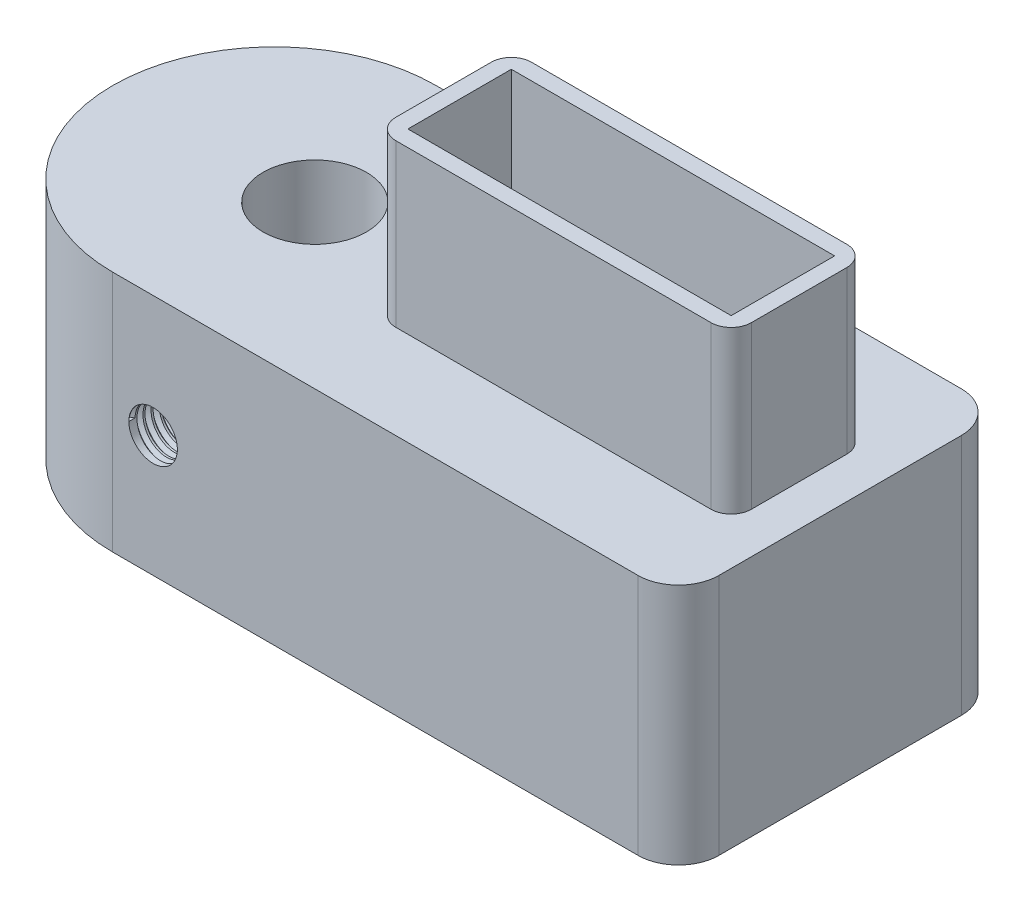
SolidWorks part; units mm, degrees
ref_plane "Front Plane" through (0, 0, 0) normal (0, 0, 1) x (1, 0, 0)
ref_plane "Top Plane" through (0, 0, 0) normal (0, 1, 0) x (1, 0, 0)
ref_plane "Right Plane" through (0, 0, 0) normal (1, 0, 0) x (0, 0, -1)
sketch "Sketch1" plane through (0, 0, 0) normal (0, 1, 0) x (1, 0, 0)
  line L1 (-22.5, 10) -> (22.5, 10)
  line L2 (-22.5, 10) -> (-22.5, -10)
  line L3 (-22.5, -10) -> (22.5, -10)
  line L4 (22.5, 10) -> (22.5, -10)
  line L5 (-22.5, 10) -> (22.5, -10) construction
  line L6 (-22.5, -10) -> (22.5, 10) construction
  point P0 (0, 0)
  dimension "D1" = 45
  dimension "D2" = 20
extrude "Boss-Extrude1" add sketch "Sketch1" along normal blind 15
sketch "Sketch2" plane through (0, 15, 0) normal (0, 1, 0) x (1, 0, 0)
  line L0 (-22.5, 10) -> (-22.5, -10) construction
  circle A0 centre (-10, 0) radius 3.2
  dimension "D1" = 12.5
extrude "Cut-Extrude1" cut sketch "Sketch2" against normal blind 15
sketch "Sketch3" plane through (0, 0, 10) normal (0, 0, 1) x (1, 0, 0)
  line L0 (-22.5, 7.5) -> (22.5, 7.5) construction
  line L1 (-22.5, 15) -> (-22.5, 0) construction
  line L2 (22.5, 15) -> (22.5, 0) construction
  line L3 (-10, 15) -> (-10, 0) construction
  line L4 (-22.5, 15) -> (22.5, 15) construction
  line L5 (-22.5, 0) -> (22.5, 0) construction
  circle A0 centre (-10, 7.5) radius 1.5
  dimension "D1" = 12.5
extrude "Cut-Extrude2" cut sketch "Sketch3" against normal blind 7.5
fillet "Fillet2" radius 10 2 edges at (-22.5, 7.5, -10) (-22.5, 7.5, 10)
thread "Thread1" pitch 0.5 method cut profile "Thread Profile1" start angle 0, offset 0, length 6.7, pitch 0.5, diameter 3
ref_plane "Plane1" through (-11.5, 7.5, 10) normal (0, -1, 0) x (-1, 0, 0)
sketch "Thread Profile1" plane through (-11.5, 7.5, 10) normal (0, -1, 0) x (-1, 0, 0)
  line L0 (0, 0) -> (0, 0.5) construction
  line L1 (0, 0) -> (0.2706, 0.1562)
  line L2 (0.2706, 0.1562) -> (0.2706, 0.2187)
  line L3 (0.2706, 0.2187) -> (0, 0.375)
  line L4 (0.2706, 0.1875) -> (0, 0.1875) construction
  line L11 (0, 0) -> (0, 0.375)
  point P2 (0, 0)
  dimension "Pitch" = 0.5
  dimension "Profile_Angle" = 60
  dimension "Profile_Land" = 0.0625
  dimension "Profile_Height" = 0.2706
fillet "Fillet3" radius 2.5 2 edges at (22.5, 7.5, -10) (22.5, 7.5, 10)
sketch "Sketch4" plane through (0, 15, 0) normal (0, 1, 0) x (1, 0, 0)
  line L0 (-22.5, 0) -> (22.5, 0) construction
  line L1 (22.5, -7.5) -> (22.5, 7.5) construction
  line L2 (-1.04, 0) -> (-1.04, 3.2) construction
  line L3 (-1.04, 0) -> (-1.04, -3.2) construction
  line L4 (18.96, 3.2) -> (18.96, -3.2) construction
  line L5 (-1.04, 3.2) -> (18.96, 3.2) construction
  line L6 (-1.04, -3.2) -> (18.96, -3.2) construction
  line L7 (-2.04, 4.2) -> (19.96, 4.2) construction
  line L8 (-2.04, -4.2) -> (19.96, -4.2) construction
  line L10 (-2.04, 4.2) -> (19.96, 4.2)
  line L11 (-2.04, 4.2) -> (-2.04, -4.2)
  line L12 (-2.04, -4.2) -> (19.96, -4.2)
  line L13 (19.96, 4.2) -> (19.96, -4.2)
  circle A0 centre (-10, 0) radius 3.2 construction
  dimension "D1" = 3.2
  dimension "D2" = 8.96
  dimension "D3" = 3.2
  dimension "D4" = 20
  dimension "D5" = 22
  dimension "D6" = 1
  dimension "D7" = 1
  dimension "D8" = 1
extrude "Boss-Extrude2" add sketch "Sketch4" along normal blind 10
sketch "Sketch5" plane through (0, 25, 0) normal (0, 1, 0) x (1, 0, 0)
  line L0 (-22.5, 0) -> (22.5, 0) construction
  line L1 (22.5, -7.5) -> (22.5, 7.5) construction
  line L2 (-1.04, 0) -> (-1.04, 3.2) construction
  line L3 (-1.04, 0) -> (-1.04, -3.2) construction
  line L4 (19.96, -4.2) -> (19.96, 4.2) construction
  line L5 (-1.04, 3.2) -> (18.96, 3.2)
  line L6 (-1.04, 3.2) -> (-1.04, -3.2)
  line L7 (-1.04, -3.2) -> (18.96, -3.2)
  line L8 (18.96, 3.2) -> (18.96, -3.2)
  circle A0 centre (-10, 0) radius 3.2 construction
  dimension "D1" = 8.96
  dimension "D2" = 3.2
  dimension "D3" = 3.2
  dimension "D4" = 1
extrude "Cut-Extrude3" cut sketch "Sketch5" against normal blind 25
fillet "Fillet4" radius 1.25 4 edges at (-2.04, 20, 4.2) (19.96, 20, 4.2) (19.96, 20, -4.2) (-2.04, 20, -4.2)
